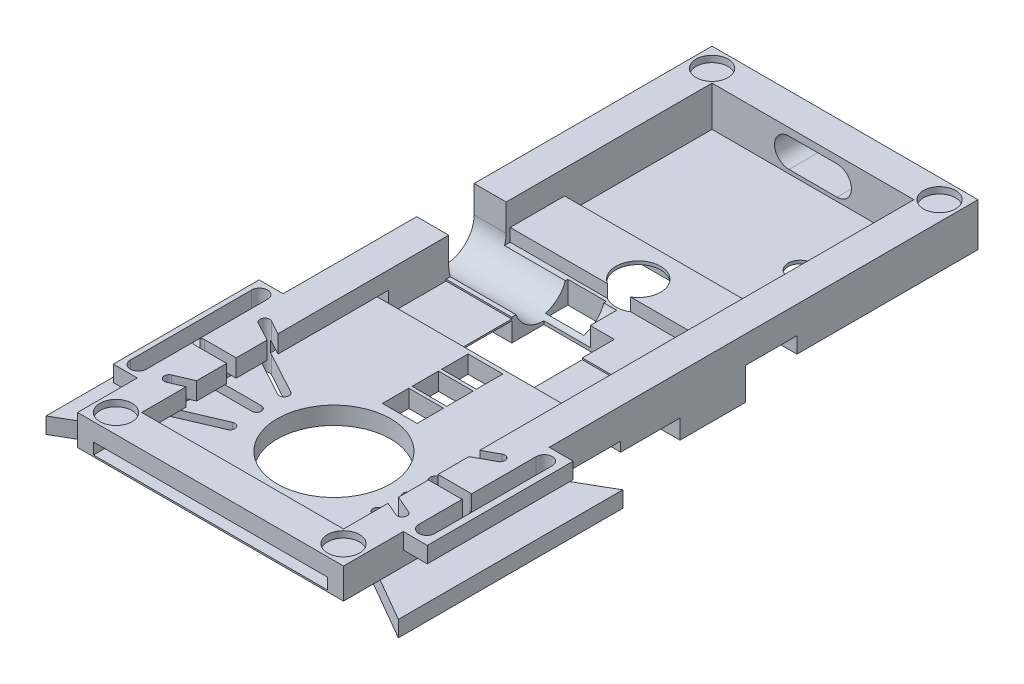
SolidWorks part; units mm, degrees
ref_plane "Front Plane" through (0, 0, 0) normal (0, 0, 1) x (1, 0, 0)
ref_plane "Top Plane" through (0, 0, 0) normal (0, 1, 0) x (1, 0, 0)
ref_plane "Right Plane" through (0, 0, 0) normal (1, 0, 0) x (0, 0, -1)
sketch "Sketch2" plane through (0, 0, 0) normal (0, 1, 0) x (1, 0, 0)
  line L1 (41.5, 99) -> (-41.5, 99)
  line L2 (41.5, 99) -> (41.5, -99)
  line L3 (41.5, -99) -> (-41.5, -99)
  line L4 (-41.5, 99) -> (-41.5, -99)
  line L5 (41.5, 99) -> (-41.5, -99) construction
  line L6 (41.5, -99) -> (-41.5, 99) construction
  point P0 (0, 0)
  dimension "D1" = 198
  dimension "D2" = 83
extrude "Boss-Extrude5" add sketch "Sketch2" along normal blind 2.5
sketch "Sketch5" plane through (0, 2.5, 0) normal (0, 1, 0) x (1, 0, 0)
  line L1 (41.5, 99) -> (-41.5, 99)
  line L2 (41.5, 99) -> (41.5, -99)
  line L3 (41.5, -99) -> (-41.5, -99)
  line L4 (-41.5, 99) -> (-41.5, -99)
  line L5 (41.5, 99) -> (-41.5, -99) construction
  line L6 (41.5, -99) -> (-41.5, 99) construction
  line L7 (31.5, 89) -> (-31.5, 89)
  line L8 (31.5, 89) -> (31.5, -89)
  line L9 (31.5, -89) -> (-31.5, -89)
  line L10 (-31.5, 89) -> (-31.5, -89)
  line L11 (31.5, 89) -> (-31.5, -89) construction
  line L12 (31.5, -89) -> (-31.5, 89) construction
  point P0 (0, 0)
  point P7 (0, 0)
  dimension "D1" = 178
  dimension "D2" = 63
extrude "Boss-Extrude6" add sketch "Sketch5" along normal blind 12
sketch "Sketch6" plane through (0, 14.5, 0) normal (0, 1, 0) x (1, 0, 0)
  line L0 (-41.5, -99) -> (41.5, -99) construction
  line L1 (-41.5, 99) -> (-41.5, -99) construction
  line L3 (41.5, 99) -> (-41.5, 99) construction
  line L4 (41.5, -99) -> (41.5, 99) construction
  circle A0 centre (-35.5, -93) radius 5
  circle A1 centre (35.5, -93) radius 5
  circle A2 centre (35.5, 93) radius 5
  circle A3 centre (-35.5, 93) radius 5
  dimension "D1" = 10
  dimension "D2" = 6
  dimension "D3" = 6
  dimension "D6" = 6
  dimension "D7" = 6
  dimension "D8" = 6
  dimension "D4" = 2
  dimension "D5" = 2
extrude "Cut-Extrude1" cut sketch "Sketch6" against normal blind 2
sketch "Sketch9" plane through (0, 0, 0) normal (0, -1, 0) x (-1, 0, 0)
  text T0 "COW-A-BUNGA" font "Cooper Black" height 3.5
extrude "Cut-Extrude2" cut sketch "Sketch9" against normal blind 1
sketch "Sketch11" plane through (0, 0, 0) normal (0, -1, 0) x (1, 0, 0)
  line L1 (-41.5, 99) -> (41.5, 99)
  line L2 (-41.5, 99) -> (-41.5, -99)
  line L3 (-41.5, -99) -> (41.5, -99)
  line L4 (41.5, 99) -> (41.5, -99)
extrude "Cut-Extrude4" cut sketch "Sketch11" against normal blind 3
sketch "Sketch12" plane through (0, 3, 0) normal (0, -1, 0) x (-1, 0, 0)
  line L0 (41.5, -99) -> (41.5, 99) construction
  line L1 (41.5, 43) -> (31.5, 43)
  line L2 (41.5, 43) -> (41.5, 89)
  line L4 (31.5, 43) -> (31.5, 89)
  line L5 (-41.5, 99) -> (-41.5, -99) construction
  line L6 (31.5, 89) -> (-31.5, 89)
  line L7 (41.5, 89) -> (41.5, 99)
  line L8 (41.5, 99) -> (-41.5, 99)
  line L9 (-41.5, 89) -> (-41.5, 99)
  line L11 (-31.5, 89) -> (-31.5, 43)
  line L12 (-31.5, 43) -> (-41.5, 43)
  line L13 (-41.5, 89) -> (-41.5, 43)
  point P17 (-36.5, 43)
  dimension "D1" = 56
  dimension "D2" = 56
extrude "Boss-Extrude9" add sketch "Sketch12" along normal blind 1
sketch "Sketch14" plane through (0, 2, 0) normal (0, -1, 0) x (1, 0, 0)
  line L1 (-41.5, -43) -> (41.5, -43)
  line L2 (-41.5, -43) -> (-41.5, -99)
  line L3 (-41.5, -99) -> (41.5, -99)
  line L4 (41.5, -43) -> (41.5, -99)
extrude "Boss-Extrude10" add sketch "Sketch14" along normal blind 1
sketch "Sketch15" plane through (0, 1, 0) normal (0, -1, 0) x (1, 0, 0)
  line L0 (-41.5, -99) -> (41.5, -99) construction
  line L1 (41.5, -99) -> (41.5, -43) construction
  circle A0 centre (20.25, -64.75) radius 3.75
  dimension "D1" = 7.5
  dimension "D2" = 34.25
  dimension "D3" = 21.25
sketch "Sketch16" plane through (0, 3, 0) normal (0, -1, 0) x (1, 0, 0)
  line L0 (41.5, -43) -> (41.5, 99) construction
  line L1 (-41.5, -43) -> (41.5, -43)
  line L2 (-41.5, -43) -> (-41.5, -26)
  line L3 (-41.5, -26) -> (41.5, -26)
  line L4 (41.5, -43) -> (41.5, -26)
  line L6 (-41.5, -26) -> (41.5, -26)
  line L7 (-41.5, -26) -> (-41.5, -6)
  line L8 (-41.5, -6) -> (41.5, -6)
  line L9 (41.5, -26) -> (41.5, -6)
  dimension "D1" = 17
  dimension "D2" = 20
extrude "Cut-Extrude6" cut sketch "Sketch16" against normal blind 4 contours L3 L4 L1 L2
sketch "Sketch17" plane through (0, 7, 0) normal (0, -1, 0) x (1, 0, 0)
  line L1 (-41.5, -26) -> (41.5, -26)
  line L2 (-41.5, -26) -> (-41.5, -43)
  line L3 (-41.5, -43) -> (41.5, -43)
  line L4 (41.5, -26) -> (41.5, -43)
extrude "Boss-Extrude13" add sketch "Sketch17" along normal blind 1
sketch "Sketch19" plane through (0, 0, -43) normal (0, 0, 1) x (1, 0, 0)
  line L1 (-41.5, 6) -> (41.5, 6)
  line L2 (-41.5, 6) -> (-41.5, 1)
  line L3 (-41.5, 1) -> (41.5, 1)
  line L4 (41.5, 6) -> (41.5, 1)
extrude "Boss-Extrude18" add sketch "Sketch19" along normal blind 0.5
sketch "Sketch20" plane through (0, 3, 0) normal (0, -1, 0) x (1, 0, 0)
  line L0 (41.5, -26) -> (41.5, 99) construction
  line L1 (-41.5, -26) -> (41.5, -26)
  line L2 (-41.5, -26) -> (-41.5, -6)
  line L3 (-41.5, -6) -> (41.5, -6)
  line L4 (41.5, -26) -> (41.5, -6)
  dimension "D1" = 20
extrude "Boss-Extrude22" add sketch "Sketch20" along normal blind 7
sketch "Sketch22" plane through (0, 0, -26) normal (0, 0, -1) x (-1, 0, 0)
  line L1 (-41.5, 6) -> (41.5, 6)
  line L2 (-41.5, 6) -> (-41.5, -4)
  line L3 (-41.5, -4) -> (41.5, -4)
  line L4 (41.5, 6) -> (41.5, -4)
extrude "Boss-Extrude23" add sketch "Sketch22" along normal blind 0.5
sketch "Sketch23" plane through (0, 3, 0) normal (0, -1, 0) x (-1, 0, 0)
  line L1 (-41.5, 6) -> (41.5, 6)
  line L2 (-41.5, 6) -> (-41.5, -99)
  line L3 (-41.5, -99) -> (41.5, -99)
  line L4 (41.5, 6) -> (41.5, -99)
extrude "Cut-Extrude8" cut sketch "Sketch23" against normal blind 3
sketch "Sketch26" plane through (0, 6, 0) normal (0, -1, 0) x (-1, 0, 0)
  line L0 (31.5, -89) -> (31.5, 6) construction
  line L1 (41.5, 6) -> (31.5, 6)
  line L2 (41.5, 6) -> (41.5, -12)
  line L3 (41.5, -12) -> (31.5, -12)
  line L4 (31.5, 6) -> (31.5, -12)
  line L5 (-41.5, 6) -> (-41.5, -99) construction
  line L6 (-31.5, 6) -> (-41.5, 6)
  line L7 (-31.5, 6) -> (-31.5, -12)
  line L8 (-31.5, -12) -> (-41.5, -12)
  line L9 (-41.5, 6) -> (-41.5, -12)
  dimension "D1" = 18
  dimension "D2" = 18
extrude "Boss-Extrude28" add sketch "Sketch26" along normal blind 3.5
sketch "Sketch27" plane through (0, 2.5, 0) normal (0, -1, 0) x (1, 0, 0)
  line L1 (-41.5, 12) -> (41.5, 12)
  line L2 (-41.5, 12) -> (-41.5, -6)
  line L3 (-41.5, -6) -> (41.5, -6)
  line L4 (41.5, 12) -> (41.5, -6)
extrude "Boss-Extrude29" add sketch "Sketch27" along normal blind 0.5
sketch "Sketch28" plane through (0, 6, 0) normal (0, -1, 0) x (1, 0, 0)
  line L1 (-41.5, 12) -> (41.5, 12)
  line L2 (-41.5, 12) -> (-41.5, 99)
  line L3 (-41.5, 99) -> (41.5, 99)
  line L4 (41.5, 12) -> (41.5, 99)
extrude "Cut-Extrude9" cut sketch "Sketch28" against normal blind 3
sketch "Sketch29" plane through (0, 9, 0) normal (0, -1, 0) x (-1, 0, 0)
  line L0 (-41.5, -99) -> (41.5, -99) construction
  line L1 (41.5, -12) -> (36.5, -12)
  line L2 (41.5, -12) -> (41.5, -99)
  line L3 (41.5, -99) -> (36.5, -99)
  line L4 (36.5, -12) -> (36.5, -99)
  dimension "D1" = 5
extrude "Boss-Extrude34" add sketch "Sketch29" along normal blind 3.5
sketch "Sketch30" plane through (0, 9, 0) normal (0, -1, 0) x (-1, 0, 0)
  line L0 (-41.5, -99) -> (36.5, -99) construction
  line L1 (-41.5, -12) -> (-36.5, -12)
  line L2 (-41.5, -12) -> (-41.5, -99)
  line L3 (-41.5, -99) -> (-36.5, -99)
  line L4 (-36.5, -12) -> (-36.5, -99)
  dimension "D1" = 5
extrude "Boss-Extrude35" add sketch "Sketch30" along normal blind 3.5
sketch "Sketch31" plane through (0, 5.5, 0) normal (0, -1, 0) x (-1, 0, 0)
  line L1 (41.5, -12) -> (-41.5, -12)
  line L2 (41.5, -12) -> (41.5, -99)
  line L3 (41.5, -99) -> (-41.5, -99)
  line L4 (-41.5, -12) -> (-41.5, -99)
extrude "Boss-Extrude36" add sketch "Sketch31" along normal blind 0.5
sketch "Sketch32" plane through (0, 0, 12) normal (0, 0, 1) x (1, 0, 0)
  line L1 (-41.5, 5) -> (41.5, 5)
  line L2 (-41.5, 5) -> (-41.5, 2)
  line L3 (-41.5, 2) -> (41.5, 2)
  line L4 (41.5, 5) -> (41.5, 2)
extrude "Boss-Extrude37" add sketch "Sketch32" along normal blind 0.5
sketch "Sketch33" plane through (0, 5, 0) normal (0, -1, 0) x (1, 0, 0)
  line L0 (-41.5, 99) -> (-41.5, 12.5) construction
  line L1 (41.5, 99) -> (-41.5, 99) construction
  line L2 (41.5, 12.5) -> (-41.5, 12.5) construction
  line L3 (-6, 40.5) -> (6, 40.5)
  line L4 (-6, 40.5) -> (-6, 12.5)
  line L5 (-6, 12.5) -> (6, 12.5)
  line L6 (6, 40.5) -> (6, 12.5)
  line L7 (41.5, 12.5) -> (41.5, 99) construction
  circle A0 centre (0, 60.5) radius 18.5
  dimension "D1" = 37
  dimension "D2" = 41.5
  dimension "D3" = 38.5
  dimension "D4" = 47.5
  dimension "D5" = 47.5
  dimension "D6" = 28
extrude "Boss-Extrude39" add sketch "Sketch33" along normal blind 5
sketch "Sketch35" plane through (0, 0, 0) normal (0, -1, 0) x (1, 0, 0)
  line L0 (-18.5, 60.5) -> (18.5, 60.5) construction
  line L1 (0, 79) -> (0, 42)
  circle A0 centre (0, 60.5) radius 18.5 construction
  circle A1 centre (0, 60.5) radius 17.6713
extrude "Cut-Extrude11" cut sketch "Sketch35" against normal blind 25 contours A1
sketch "Sketch36" plane through (0, 0, 0) normal (0, -1, 0) x (-1, 0, 0)
  line L0 (6, -12.5) -> (-6, -12.5) construction
  line L1 (5.3705, -40) -> (-5.4626, -40)
  line L2 (5.3705, -40) -> (5.3705, -31.75)
  line L3 (5.3705, -31.75) -> (-5.4626, -31.75)
  line L4 (-5.4626, -40) -> (-5.4626, -31.75)
  line L5 (5.3705, -30.75) -> (-5.4626, -30.75)
  line L6 (5.3705, -30.75) -> (5.3705, -22.5)
  line L7 (5.3705, -22.5) -> (-5.4626, -22.5)
  line L8 (-5.4626, -30.75) -> (-5.4626, -22.5)
  line L9 (5.3705, -21.5) -> (-5.4626, -21.5)
  line L10 (5.3705, -21.5) -> (5.3705, -13.25)
  line L11 (5.3705, -13.25) -> (-5.4626, -13.25)
  line L12 (-5.4626, -21.5) -> (-5.4626, -13.25)
  dimension "D1" = 8.25
  dimension "D2" = 8.25
  dimension "D3" = 8.25
  dimension "D4" = 0.75
  dimension "D5" = 1
  dimension "D6" = 1
extrude "Cut-Extrude12" cut sketch "Sketch36" against normal blind 25
sketch "Sketch37" plane through (0, 5, 0) normal (0, -1, 0) x (-1, 0, 0)
  line L0 (-16.0152, -72.861) -> (-54.9864, -95.361)
  line L1 (-54.9864, -95.361) -> (-54.9864, -25.3367)
  line L2 (-54.9864, -25.3367) -> (-16.0152, -47.8367)
  line L3 (0, -42.8287) -> (0, -79) construction
  line L4 (54.9864, -95.361) -> (54.9864, -25.3367)
  line L5 (16.0152, -72.861) -> (54.9864, -95.361)
  line L6 (54.9864, -25.3367) -> (16.0152, -47.8367)
  arc A0 (-16.0152, -47.8367) -> (-16.0152, -72.861) centre (-3.5031, -60.3488) ccw
  circle A1 centre (0, -60.5) radius 17.6713 construction
  circle A2 centre (0, -60.5) radius 18.5 construction
  arc A3 (16.0152, -47.8367) -> (16.0152, -72.861) centre (3.5031, -60.3488) cw
  dimension "D1" = 60
  dimension "D2" = 60
  dimension "D3" = 45
extrude "Boss-Extrude42" add sketch "Sketch37" along normal blind 5
sketch "Sketch38" plane through (0, -4, 0) normal (0, -1, 0) x (1, 0, 0)
  line L0 (41.5, 99) -> (-41.5, 99) construction
  line L1 (-11, -16) -> (11, -16)
  line L2 (-11, -16) -> (-11, 12)
  line L3 (-11, 12) -> (11, 12)
  line L4 (11, -16) -> (11, 12)
  line L5 (41.5, -6) -> (41.5, 12.5) construction
  point P6 (0, -16)
  dimension "D1" = 115
  dimension "D2" = 28
  dimension "D3" = 22
  dimension "D4" = 52.5
extrude "Cut-Extrude13" cut sketch "Sketch38" against normal blind 25
sketch "Sketch39" plane through (0, -4, 0) normal (0, -1, 0) x (1, 0, 0)
  line L1 (-12.5, -18) -> (-0.5, -18)
  line L2 (-12.5, -18) -> (-12.5, -25)
  line L3 (-12.5, -25) -> (-0.5, -25)
  line L4 (-0.5, -18) -> (-0.5, -25)
  line L6 (-41.5, -99) -> (41.5, -99) construction
  line L7 (41.5, -26.5) -> (41.5, -6) construction
  circle A0 centre (2.4851, -32) radius 7
  point P6 (-12.5, -21.5)
  dimension "D5" = 14
  dimension "D6" = 67
  dimension "D1" = 81
  dimension "D2" = 7
  dimension "D3" = 54
  dimension "D4" = 12
extrude "Cut-Extrude14" cut sketch "Sketch39" against normal blind 25
extrude "Cut-Extrude15" cut sketch "Sketch15" against normal blind 25 contours A0
sketch "Sketch40" plane through (-41.5, 0, 0) normal (-1, 0, 0) x (0, 0, 1)
  line L0 (-15.7893, 47.6037) -> (-15.7893, 5.9968) construction
  line L1 (-6.8278, 47.6037) -> (-6.8278, 5.9968)
  line L2 (-24.7508, 47.6037) -> (-24.7508, 5.9968)
  arc A0 (-6.8278, 47.6037) -> (-24.7508, 47.6037) centre (-15.7893, 47.6037) ccw
  arc A1 (-24.7508, 5.9968) -> (-6.8278, 5.9968) centre (-15.7893, 5.9968) ccw
  point P2 (-15.7893, 26.8003)
  point P7 (0, 0)
  point P8 (0, 0)
  point P9 (0, 0)
  point P10 (-24.9642, 46.5369)
extrude "Cut-Extrude17" cut sketch "Sketch40" against normal blind 45
sketch "Sketch41" plane through (41.5, 0, 0) normal (1, 0, 0) x (0, 0, -1)
  line L0 (-99, 14.5) -> (99, 14.5) construction
  line L1 (-80.3542, 14.5) -> (-34.8306, 14.5)
  line L2 (-80.3542, 14.5) -> (-80.3542, 9.5)
  line L3 (-80.3542, 9.5) -> (-34.8306, 9.5)
  line L4 (-34.8306, 14.5) -> (-34.8306, 9.5)
  dimension "D1" = 5
extrude "Boss-Extrude44" add sketch "Sketch41" along normal blind 7.5
sketch "Sketch42" plane through (0, 14.5, 0) normal (0, 1, 0) x (1, 0, 0)
  line L0 (44.4812, -39.3477) -> (44.4812, -75.9668) construction
  line L1 (46.9812, -39.3477) -> (46.9812, -75.9668)
  line L2 (41.9812, -39.3477) -> (41.9812, -75.9668)
  arc A0 (46.9812, -39.3477) -> (41.9812, -39.3477) centre (44.4812, -39.3477) ccw
  arc A1 (41.9812, -75.9668) -> (46.9812, -75.9668) centre (44.4812, -75.9668) ccw
  point P2 (44.4812, -57.6573)
  point P7 (0, 0)
  point P8 (44.5089, -76.2377)
  point P9 (0, 0)
  point P10 (0, 0)
  point P11 (0, 0)
  point P12 (0, 0)
  point P13 (0, 0)
  point P14 (41.9812, -75.9668)
  dimension "D1" = 5
extrude "Cut-Extrude18" cut sketch "Sketch42" against normal blind 7.5
sketch "Sketch43" plane through (0, 14.5, 0) normal (0, 1, 0) x (1, 0, 0)
  line L0 (41.5, -34.8306) -> (-41.5, -34.8306) construction
  line L1 (-41.5, 6.8278) -> (-41.5, -99) construction
  line L2 (41.5, -80.3542) -> (-41.5, -80.3542) construction
  line L4 (-41.5, -34.8306) -> (-49, -34.8306)
  line L5 (-41.5, -34.8306) -> (-41.5, -80.3542)
  line L6 (-41.5, -80.3542) -> (-49, -80.3542)
  line L7 (-49, -34.8306) -> (-49, -80.3542)
  dimension "D1" = 7.5
extrude "Boss-Extrude46" add sketch "Sketch43" against normal blind 5
sketch "Sketch44" plane through (0, 14.5, 0) normal (0, 1, 0) x (1, 0, 0)
  line L0 (-44.9421, -38.7585) -> (-44.9421, -76.5876) construction
  line L1 (-42.4421, -38.7585) -> (-42.4421, -76.5876)
  line L2 (-47.4421, -38.7585) -> (-47.4421, -76.5876)
  arc A0 (-42.4421, -38.7585) -> (-47.4421, -38.7585) centre (-44.9421, -38.7585) ccw
  arc A1 (-47.4421, -76.5876) -> (-42.4421, -76.5876) centre (-44.9421, -76.5876) ccw
  point P2 (-44.9421, -57.6731)
  dimension "D1" = 5
extrude "Cut-Extrude19" cut sketch "Sketch44" against normal blind 5
sketch "Sketch46" plane through (0, 0, -99) normal (0, 0, -1) x (-1, 0, 0)
  line L0 (7.5, 7.6848) -> (-7.5, 7.6848) construction
  line L1 (7.5, 3.1848) -> (-7.5, 3.1848)
  line L2 (7.5, 12.1848) -> (-7.5, 12.1848)
  line L3 (-41.5, 9.5) -> (-41.5, 14.5) construction
  arc A0 (7.5, 3.1848) -> (7.5, 12.1848) centre (7.5, 7.6848) ccw
  arc A1 (-7.5, 12.1848) -> (-7.5, 3.1848) centre (-7.5, 7.6848) ccw
  point P2 (0, 7.6848)
  dimension "D1" = 15
  dimension "D2" = 41.5
  dimension "D3" = 9
extrude "Cut-Extrude20" cut sketch "Sketch46" against normal blind 15
sketch "Sketch47" plane through (0, 0, 0) normal (0, -1, 0) x (-1, 0, 0)
  line L0 (-23.6471, -60.9929) -> (-41.434, -60.9929) construction
  line L1 (-23.6471, -62.4929) -> (-41.434, -62.4929)
  line L2 (-23.6471, -59.4929) -> (-41.434, -59.4929)
  line L3 (-23.5161, -52.4991) -> (-36.7134, -45.3342) construction
  line L4 (-24.2318, -53.8173) -> (-37.429, -46.6524)
  line L5 (-22.8004, -51.1808) -> (-35.9977, -44.0159)
  line L6 (-23.0572, -69.8686) -> (-36.3509, -75.5543) construction
  line L7 (-22.4674, -71.2477) -> (-35.761, -76.9335)
  line L8 (-23.6471, -68.4894) -> (-36.9407, -74.1752)
  line L9 (0, -42.8287) -> (0, -78.1713) construction
  line L10 (23.0572, -69.8686) -> (36.3509, -75.5543) construction
  line L11 (22.4674, -71.2477) -> (35.761, -76.9335)
  line L12 (23.6471, -68.4894) -> (36.9407, -74.1752)
  line L13 (23.6471, -60.9929) -> (41.434, -60.9929) construction
  line L14 (23.6471, -62.4929) -> (41.434, -62.4929)
  line L15 (23.6471, -59.4929) -> (41.434, -59.4929)
  line L16 (23.5161, -52.4991) -> (36.7134, -45.3342) construction
  line L17 (24.2318, -53.8173) -> (37.429, -46.6524)
  line L18 (22.8004, -51.1808) -> (35.9977, -44.0159)
  arc A0 (-23.6471, -62.4929) -> (-23.6471, -59.4929) centre (-23.6471, -60.9929) ccw
  arc A1 (-41.434, -59.4929) -> (-41.434, -62.4929) centre (-41.434, -60.9929) ccw
  arc A2 (-24.2318, -53.8173) -> (-22.8004, -51.1808) centre (-23.5161, -52.4991) ccw
  arc A3 (-35.9977, -44.0159) -> (-37.429, -46.6524) centre (-36.7134, -45.3342) ccw
  arc A4 (-22.4674, -71.2477) -> (-23.6471, -68.4894) centre (-23.0572, -69.8686) ccw
  arc A5 (-36.9407, -74.1752) -> (-35.761, -76.9335) centre (-36.3509, -75.5543) ccw
  circle A6 centre (0, -60.5) radius 17.6713 construction
  arc A7 (22.4674, -71.2477) -> (23.6471, -68.4894) centre (23.0572, -69.8686) cw
  arc A8 (36.9407, -74.1752) -> (35.761, -76.9335) centre (36.3509, -75.5543) cw
  arc A9 (23.6471, -62.4929) -> (23.6471, -59.4929) centre (23.6471, -60.9929) cw
  arc A10 (41.434, -59.4929) -> (41.434, -62.4929) centre (41.434, -60.9929) cw
  arc A11 (24.2318, -53.8173) -> (22.8004, -51.1808) centre (23.5161, -52.4991) cw
  arc A12 (35.9977, -44.0159) -> (37.429, -46.6524) centre (36.7134, -45.3342) cw
  point P2 (-32.5405, -60.9929)
  point P7 (-30.1147, -48.9166)
  point P14 (-29.704, -72.7114)
  point P23 (29.704, -72.7114)
  point P35 (32.5405, -60.9929)
  point P42 (30.1147, -48.9166)
  dimension "D1" = 3
  dimension "D2" = 3
  dimension "D3" = 3
extrude "Cut-Extrude23" cut sketch "Sketch47" against normal blind 15
